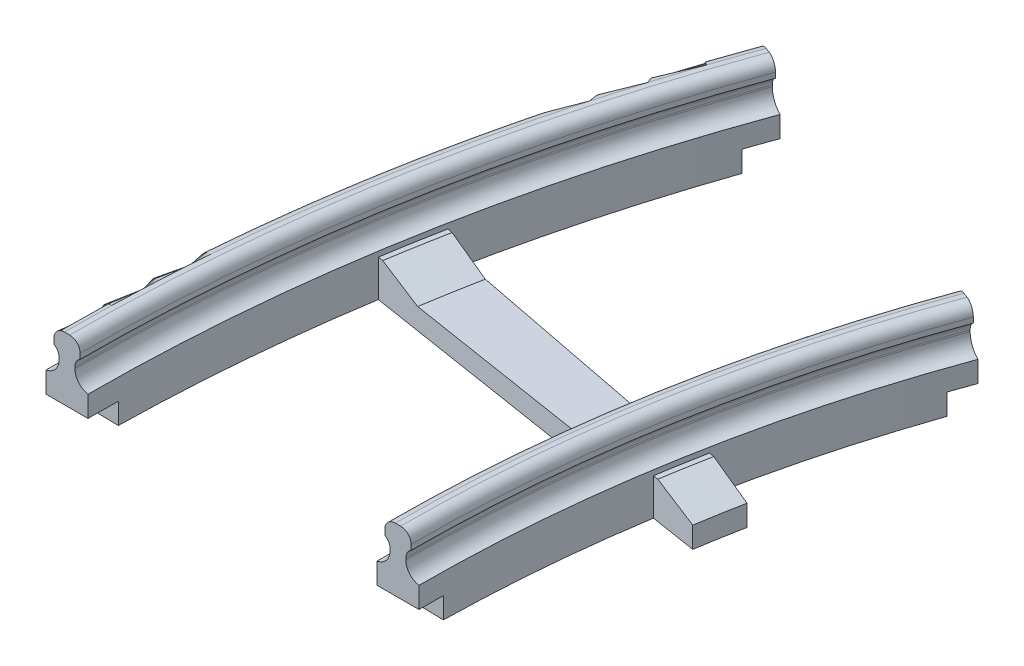
SolidWorks part; units mm, degrees
other "标注1"
sketch "草图3" plane through (-22.25, 4, -10) normal (-0.231, 0.6469, -0.7268) x (-0.9696, -0.2151, 0.1167)
ref_plane "前视基准面" through (0, 0, 0) normal (0, 0, 1) x (1, 0, 0)
ref_plane "上视基准面" through (0, 0, 0) normal (0, 1, 0) x (1, 0, 0)
ref_plane "右视基准面" through (0, 0, 0) normal (1, 0, 0) x (0, 0, -1)
other "Configuration Table"
sketch "草图4" plane through (0, 0, 0) normal (0, 0, 1) x (1, 0, 0)
  line L0 (0, 0) -> (31.5, 0) construction
  line L1 (0.75, -1.5) -> (1.25, -1.5)
  line L3 (0, 0) -> (1.25, 0)
  line L4 (1.25, -1.5) -> (1.25, 0)
  line L5 (0, 0) -> (-1.25, 0)
  line L10 (0.75, -1.5) -> (0.75, -4)
  line L11 (-0.75, -1.5) -> (-1.25, -1.5)
  line L12 (0.75, -4) -> (2, -4)
  line L14 (0, -8) -> (2, -8)
  line L15 (2, -4) -> (2, -8)
  line L16 (-1.25, 0) -> (-1.25, -1.5)
  line L20 (-0.75, -1.5) -> (-0.75, -4)
  line L21 (-0.75, -4) -> (-2, -4)
  line L23 (0, -8) -> (-2, -8)
  line L24 (-2, -4) -> (-2, -8)
  line L25 (31.5, 0) -> (32.75, 0)
  line L26 (30.25, 0) -> (31.5, 0)
  line L27 (30.25, 0) -> (30.25, -1.5)
  line L28 (30.25, -1.5) -> (30.75, -1.5)
  line L31 (30.75, -1.5) -> (30.75, -4)
  line L34 (29.5, -4) -> (30.75, -4)
  line L35 (29.5, -4) -> (29.5, -8)
  line L36 (29.5, -8) -> (31.5, -8)
  line L39 (32.25, -1.5) -> (32.75, -1.5)
  line L40 (32.75, 0) -> (32.75, -1.5)
  line L42 (32.25, -1.5) -> (32.25, -4)
  line L45 (32.25, -4) -> (33.5, -4)
  line L47 (31.5, -8) -> (33.5, -8)
  line L48 (33.5, -4) -> (33.5, -8)
  point P0 (0, 0)
  point P2 (15.75, 0)
  dimension "D1" = 1.25
  dimension "D4" = 2.5
sketch "草图6" plane through (0, 0, 0) normal (0, 0, 1) x (1, 0, 0)
  line L0 (165.75, 3.8535) -> (165.75, -12.2756)
  dimension "D1" = 150
revolve "旋转1" add sketch "草图4" angle 10 about L0
fillet "圆角1" radius 1.5 2 edges at (1.3779, -4, -14.3807) (-0.1164, -4, -14.5114)
fillet "圆角2" radius 1.5 2 edges at (31.2637, -4, -11.766) (32.758, -4, -11.6353)
fillet "圆角3" radius 1 4 edges at (33.2561, 0, -11.5917) (30.7656, 0, -11.8096) (31.2637, -1.5, -11.766) (32.758, -1.5, -11.6353)
fillet "圆角4" radius 1 4 edges at (1.876, 0, -14.3371) (-0.1164, -1.5, -14.5114) (1.3779, -1.5, -14.3807) (-0.6145, 0, -14.555)
sketch "草图7" plane through (0, 0, 0) normal (0, 0, 1) x (1, 0, 0)
  line L1 (-2, -8) -> (2, -8)
  line L2 (-2, -8) -> (-2, -6)
  line L3 (-2, -6) -> (2, -6)
  line L4 (2, -8) -> (2, -6)
  line L5 (33.5, -8) -> (33.5, -4) construction
  line L6 (29.5, -8) -> (33.5, -8)
  line L7 (29.5, -8) -> (29.5, -6)
  line L8 (29.5, -6) -> (33.5, -6)
  line L9 (33.5, -8) -> (33.5, -6)
  line L10 (2, -8) -> (2, -4) construction
  dimension "D1" = 2
sketch "草图9" plane through (0, 0, 0) normal (0, 1, 0) x (1, 0, 0)
  line L0 (29.5, 0) -> (2, 0)
  line L1 (-2, 0) -> (2, 0) construction
  line L2 (4.4877, 28.4349) -> (31.5699, 23.6596)
  line L3 (18.0288, 26.0472) -> (15.75, 0)
  arc A0 (4.4877, 28.4349) -> (2, 0) centre (165.75, 0) ccw construction
  arc A1 (31.5699, 23.6596) -> (29.5, 0) centre (165.75, 0) ccw construction
  point P20 (165.75, 0)
  dimension "D1" = 10
  dimension "D2" = 26.1467
revolve "切除-旋转1" cut sketch "草图7" angle 1 about L0
sketch "草图10" plane through (0, -6, 0) normal (0, -1, 0) x (1, 0, 0)
  line L0 (-1.9936, -1.4639) -> (2.0062, -1.429) construction
  line L2 (2.0062, -1.429) -> (29.5052, -1.189) construction
  line L3 (29.5052, -1.189) -> (33.505, -1.1541) construction
  circle A1 centre (0.0063, -1.4464) radius 0.4
  circle A2 centre (31.5051, -1.1715) radius 0.4
  arc A3 (-2, 0) -> (-1.9745, -2.9276) centre (165.75, 0) ccw construction
  arc A4 (2, 0) -> (2.0249, -2.8578) centre (165.75, 0) ccw construction
  arc A5 (29.5, 0) -> (29.5208, -2.3779) centre (165.75, 0) ccw construction
  arc A6 (33.5, 0) -> (33.5201, -2.3081) centre (165.75, 0) ccw construction
  point P10 (0, 0)
  point P24 (0, 0)
  dimension "D1" = 0.8
extrude "切除-拉伸1" cut sketch "草图10" against normal blind 2
sketch "草图11" plane through (4.998, 0, -28.3449) normal (0.1736, 0, -0.9848) x (-0.9848, 0, -0.1736)
  line L0 (-26.9819, -4.5) -> (-26.4819, -4.5)
  line L1 (-26.9819, -4) -> (-26.9819, -8) construction
  line L2 (-26.4819, -4.5) -> (-22.4819, -6)
  line L3 (-22.4819, -6) -> (-3.9819, -6)
  line L4 (-3.9819, -6) -> (0.0181, -4.5)
  line L5 (0.0181, -4.5) -> (0.5181, -4.5)
  line L6 (0.5181, -8) -> (0.5181, -4) construction
  line L7 (0.5181, -4.5) -> (4.5181, -4.5)
  line L8 (4.5181, -4) -> (4.5181, -8) construction
  line L9 (4.5181, -4.5) -> (5.0181, -4.5)
  line L10 (5.0181, -4.5) -> (9.0181, -6)
  line L11 (9.0181, -6) -> (9.0181, -8)
  line L13 (-35.4819, -8) -> (-35.4819, -6)
  line L14 (-35.4819, -6) -> (-31.4819, -4.5)
  line L15 (-31.4819, -4.5) -> (-30.9819, -4.5)
  line L16 (-30.9819, -8) -> (-30.9819, -4) construction
  line L17 (-30.9819, -4.5) -> (-26.9819, -4.5)
  line L19 (-35.4819, -8) -> (-30.9819, -8)
  line L20 (-30.9819, -8) -> (-26.9819, -8)
  line L21 (-26.9819, -8) -> (0.5181, -8)
  line L22 (0.5181, -8) -> (4.5181, -8)
  line L23 (4.5181, -8) -> (9.0181, -8)
  dimension "D1" = 0.5
  dimension "D2" = 4.5
  dimension "D3" = 3.5
  dimension "D4" = 2
revolve "旋转2" add sketch "草图11" angle 1 about L0
mirror "镜向1"
